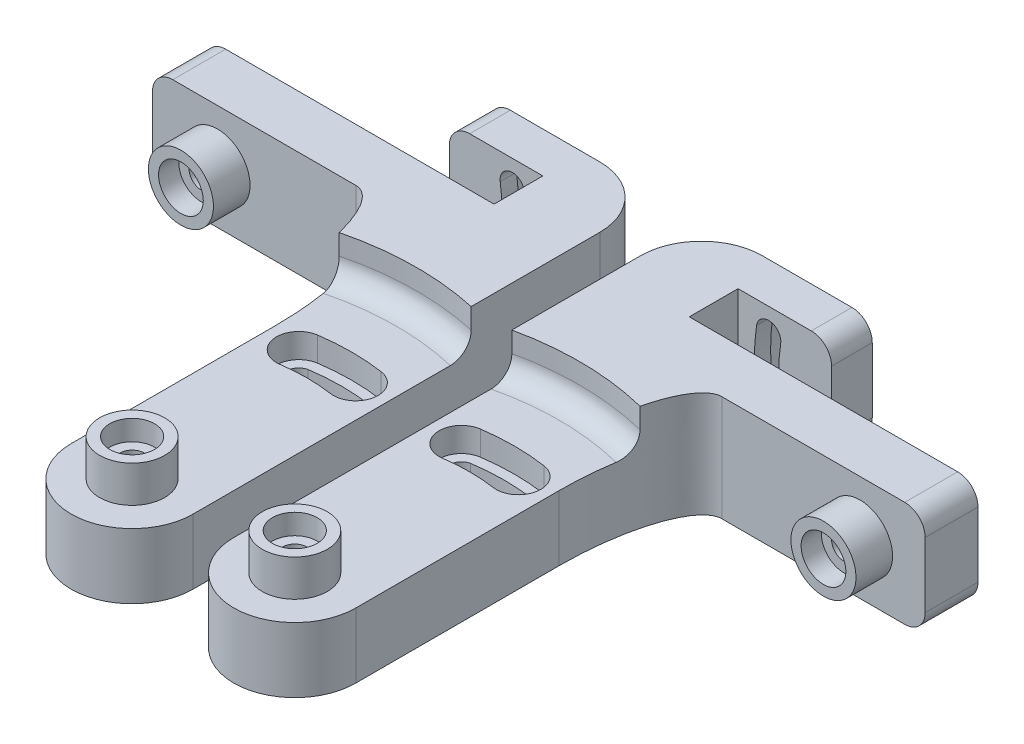
SolidWorks part; units mm, degrees
note: The reader was unsure of these and kept them because the rebuilt part matched: shared geometry of "Sketch6<8>".
ref_plane "Front Plane" through (0, 0, 0) normal (0, 0, 1) x (1, 0, 0)
ref_plane "Top Plane" through (0, 0, 0) normal (0, 1, 0) x (1, 0, 0)
ref_plane "Right Plane" through (0, 0, 0) normal (1, 0, 0) x (0, 0, -1)
sketch "Sketch1" plane through (0, 0, 0) normal (0, 1, 0) x (1, 0, 0)
  line L0 (0, 0) -> (0, 24.25) construction
  line L1 (0, -7.5) -> (0, 49000) construction
  line L2 (-7.5, 46.5) -> (-37.5, 46.5)
  line L3 (-37.5, 46.5) -> (-37.5, 42.5)
  line L5 (7.5, 0) -> (7.5, 50)
  line L6 (0, 57.5) -> (-13.5, 57.5)
  line L7 (-13.5, 57.5) -> (-13.5, 52.5)
  line L9 (-37.5, 42.5) -> (-17.5, 42.5)
  line L12 (-7.5, 0) -> (-7.5, 32.5)
  line L15 (-2, 52.5) -> (-2, 46.5)
  line L16 (-2, 46.5) -> (-7.5, 46.5)
  line L17 (-2, 52.5) -> (-13.5, 52.5)
  circle A1 centre (0, 0) radius 1.5
  arc A3 (3.5, 23.9961) -> (-3.5, 23.9961) centre (0, 0) ccw construction
  arc A4 (-3.8223, 25.4611) -> (-3.2806, 22.5122) centre (-3.5, 23.9961) ccw
  arc A5 (3.1835, 22.5262) -> (3.8663, 25.4544) centre (3.5, 23.9961) ccw
  arc A7 (3.8663, 25.4544) -> (-3.8223, 25.4611) centre (0, 0) ccw
  arc A8 (3.1835, 22.5262) -> (-3.2806, 22.5122) centre (0, 0) ccw
  arc A9 (7.5, 50) -> (0, 57.5) centre (0, 50) ccw
  arc A16 (-7.5, 0) -> (7.5, 0) centre (0, 0) ccw
  arc A17 (-7.5, 32.5) -> (-17.5, 42.5) centre (-17.5, 32.5) ccw
  dimension "D3" = 3
  dimension "D6" = 3
  dimension "D7" = 50
  dimension "D8" = 15
  dimension "D10" = 42.5
  dimension "D11" = 10
  dimension "D12" = 2
  dimension "D2" = 24.25
  dimension "D4" = 3.5
  dimension "D5" = 3.5
  dimension "D9" = 5
  dimension "D13" = 13.5
  dimension "D14" = 45
  dimension "D15" = 4
extrude "Boss-Extrude1" add sketch "Sketch1" along normal blind 8
sketch "Sketch2" plane through (0, 8, 0) normal (0, 1, 0) x (1, 0, 0)
  circle A0 centre (0, 0) radius 4
  circle A2 centre (0, 0) radius 1.5
  dimension "D1" = 8
  dimension "D2" = 3
extrude "Boss-Extrude2" add sketch "Sketch2" along normal blind 2
sketch "Sketch4" plane through (0, 10, 0) normal (0, 1, 0) x (1, 0, 0)
  circle A0 centre (0, 0) radius 4
  circle A1 centre (0, 0) radius 2.75
  dimension "D1" = 5.5
  dimension "D2" = 8
extrude "Boss-Extrude3" add sketch "Sketch4" along normal blind 2.5
sketch "Sketch5" plane through (0, 8, 0) normal (0, 1, 0) x (1, 0, 0)
  arc A0 (-3.8969, 26.7173) -> (-3.1031, 21.2749) centre (-3.5, 23.9961) ccw
  arc A1 (3.1031, 21.2749) -> (3.8969, 26.7173) centre (3.5, 23.9961) ccw
  arc A2 (3.8969, 26.7173) -> (-3.8969, 26.7173) centre (0, 0) ccw
  arc A3 (3.1031, 21.2749) -> (-3.1031, 21.2749) centre (0, 0) ccw
  dimension "D1" = 5.5
  dimension "D2" = 5.5
extrude "Cut-Extrude1" cut sketch "Sketch5" against normal blind 3
sketch "Sketch11" plane through (0, 8, 0) normal (0, 1, 0) x (1, 0, 0)
  line L0 (-2, 52.5) -> (-13.5, 52.5)
  line L3 (0, 57.5) -> (-13.5, 57.5)
  line L4 (-13.5, 57.5) -> (-13.5, 52.5)
  line L14 (-13.5, 52.5) -> (-2, 52.5)
  line L16 (-2, 46.5) -> (-37.5, 46.5)
  line L17 (-37.5, 46.5) -> (-37.5, 42.5)
  line L18 (-37.5, 42.5) -> (-17.5, 42.5)
  line L19 (-7.5, 32.5) -> (-7.5, 0)
  line L20 (7.5, 0) -> (7.5, 50)
  line L21 (0, 57.5) -> (-13.5, 57.5)
  line L27 (-2, 46.5) -> (-37.5, 46.5)
  line L28 (-37.5, 46.5) -> (-37.5, 42.5)
  line L29 (-37.5, 42.5) -> (-17.5, 42.5)
  line L30 (-7.5, 32.5) -> (-7.5, 0)
  line L31 (7.5, 0) -> (7.5, 50)
  line L34 (-13.5, 57.5) -> (-13.5, 52.5)
  line L37 (-2, 52.5) -> (-2, 46.5)
  line L38 (-2, 52.5) -> (-2, 46.5)
  arc A0 (7.5, 34.187) -> (-7.6381, 34.1564) centre (0, 0) ccw
  arc A3 (-7.5, 32.5) -> (-17.5, 42.5) centre (-17.5, 32.5) ccw
  arc A4 (-7.5, 0) -> (7.5, 0) centre (0, 0) ccw
  arc A5 (7.5, 50) -> (0, 57.5) centre (0, 50) ccw
  arc A6 (-7.5, 32.5) -> (-17.5, 42.5) centre (-17.5, 32.5) ccw
  arc A7 (-7.5, 0) -> (7.5, 0) centre (0, 0) ccw
  arc A8 (7.5, 50) -> (0, 57.5) centre (0, 50) ccw
  dimension "D2" = 35
  dimension "D1" = 0
extrude "Boss-Extrude4" add sketch "Sketch11" along normal blind 5
sketch "Sketch12" plane through (0, 0, -42.5) normal (0, 0, 1) x (1, 0, 0)
  line L8 (-37.5, 0) -> (-17.5, 0)
  line L9 (-17.5, 0) -> (-17.5, 13)
  line L10 (-17.5, 13) -> (-37.5, 13)
  line L11 (-37.5, 13) -> (-37.5, 0)
  line L12 (-37.5, 0) -> (-17.5, 0)
  line L13 (-17.5, 0) -> (-17.5, 13)
  line L14 (-17.5, 13) -> (-37.5, 13)
  line L15 (-37.5, 13) -> (-37.5, 0)
  dimension "D1" = 0
extrude "Boss-Extrude5" add sketch "Sketch12" along normal blind 2.5
sketch "Sketch14" plane through (0, 0, 0) normal (0, 1, 0) x (1, 0, 0)
  line L0 (-17.5, 30.3109) -> (-17.5, 42.5)
  arc A0 (-7.6381, 34.1564) -> (-17.5, 30.3109) centre (0, 0) ccw
  arc A1 (-7.6381, 34.1564) -> (-17.5, 42.5) centre (-17.5, 32.5) ccw construction
  arc A2 (-7.6381, 34.1564) -> (-17.5, 42.5) centre (-17.5, 32.5) ccw
extrude "Boss-Extrude6" add sketch "Sketch14" along normal up to surface (13 mm away) up to face at (-10.8799, 13, -46.5026)
sketch "Sketch15" plane through (0, 0, 0) normal (0, 1, 0) x (1, 0, 0)
  line L1 (-17.5, 30) -> (-17.5, 30.3109)
  line L2 (-17.5, 30) -> (-7.8175, 30)
  arc A0 (-7.5, 32.5) -> (-7.6381, 34.1564) centre (-17.5, 32.5) ccw construction
  arc A1 (-7.8175, 30) -> (-7.6381, 34.1564) centre (-17.5, 32.5) ccw
  arc A2 (7.5, 34.187) -> (-17.5, 30.3109) centre (0, 0) ccw construction
  arc A3 (-7.6381, 34.1564) -> (-17.5, 30.3109) centre (0, 0) ccw
extrude "Boss-Extrude7" add sketch "Sketch15" along normal up to surface (8 mm away) up to face at (-1.5211, 8, -18.8349)
sketch "Sketch6" plane through (0, 0, -57.5) normal (0, 0, -1) x (-1, 0, 0)
  line L0 (2, 0) -> (37.5, 0) construction
  line L1 (37.5, 13) -> (37.5, 0) construction
  line L2 (29.5, 6.5) -> (-18.8, 6.5) construction
  line L3 (29.5, -993.5) -> (29.5, 49006.5) construction
  circle A0 centre (29.5, 6.5) radius 1.5
  circle A1 centre (5.5, 6.5) radius 1.5 construction
  arc A3 (7.2405, 9.7812) -> (4.2726, 10.2188) centre (5.7566, 10) ccw
  arc A4 (4.2726, 2.7812) -> (7.2405, 3.2187) centre (5.7566, 3) ccw
  arc A8 (7.2405, 9.7812) -> (7.2405, 3.2187) centre (29.5, 6.5) ccw
  arc A9 (4.2726, 10.2188) -> (4.2726, 2.7812) centre (29.5, 6.5) ccw
  arc A14 (8.4772, 9.599) -> (3.036, 10.401) centre (5.7566, 10) ccw
  arc A18 (3.036, 10.401) -> (3.036, 2.599) centre (29.5, 6.5) ccw
  arc A19 (8.4772, 9.599) -> (8.4772, 3.401) centre (29.5, 6.5) ccw
  arc A20 (3.036, 2.599) -> (8.4772, 3.401) centre (5.7566, 3) ccw
  dimension "D1" = 3
  dimension "D4" = 3
  dimension "D8" = 3
  dimension "D9" = 3
  dimension "D10" = 25.5
  dimension "D11" = 5.5
  dimension "D12" = 22.5
  dimension "D13" = 2.75
  dimension "D2" = 6.5
  dimension "D3" = 24
  dimension "D5" = 8
  dimension "D6" = 3.5
  dimension "D7" = 3.5
extrude "Cut-Extrude5" cut sketch "Sketch6" against normal blind 17 contours A3 A9 A4 A8 | A0
extrude "Cut-Extrude6" cut sketch "Sketch6<8>" against normal blind 3
sketch "Sketch6<8>" plane through (0, 0, -57.5) normal (0, 0, -1) x (-1, 0, 0) same geometry as "Sketch6"
sketch "Sketch17" plane through (0, 0, -40) normal (0, 0, 1) x (1, 0, 0)
  circle A0 centre (-29.5, 6.5) radius 4
  circle A1 centre (-29.5, 6.5) radius 1.5
  dimension "D1" = 8
  dimension "D2" = 3
extrude "Boss-Extrude8" add sketch "Sketch17" along normal blind 2
sketch "Sketch18" plane through (0, 0, -38) normal (0, 0, 1) x (1, 0, 0)
  circle A0 centre (-29.5, 6.5) radius 4
  circle A1 centre (-29.5, 6.5) radius 2.75
  dimension "D1" = 5.5
  dimension "D2" = 8
extrude "Boss-Extrude9" add sketch "Sketch18" along normal blind 2.5
fillet "Fillet3" radius 2.5 5 edges at (-13.5, 0, -55) (-13.5, 13, -55) (-37.5, 0, -43.25) (-37.5, 13, -43.25) (-5.3625, 8, -34.5868)
ref_plane "Plane1" through (10, 0, 0) normal (1, 0, 0) x (0, 0, -1)
sketch "Sketch21" plane through (0, 0, -40) normal (0, 0, 1) x (1, 0, 0)
  circle A1 centre (-29.5, 6.5) radius 1.5
  circle A2 centre (-29.5, 6.5) radius 1.5
  dimension "D1" = 0
extrude "Cut-Extrude7" cut sketch "Sketch21" against normal blind 10
sketch "Sketch22" plane through (0, 13, 0) normal (0, 1, 0) x (1, 0, 0)
  line L0 (-7.5, 31.6228) -> (-7.5, 0) construction
  line L1 (-17.5, 40) -> (-7.5, 40)
  line L2 (-17.5, 40) -> (-17.5, 25)
  line L3 (-17.5, 25) -> (-7.5, 25)
  line L4 (-7.5, 40) -> (-7.5, 25)
  dimension "D1" = 15
extrude "Cut-Extrude8" cut sketch "Sketch22" against normal through all
fillet "Fillet4" radius 15 1 edges at (-7.5, 6.5, -40) second distance 5 first distance on face at (-7.5, 7.4026, -25.7634)
mirror "Mirror2" about plane through (10, 0, 0) normal (1, 0, 0) of bodies 126
